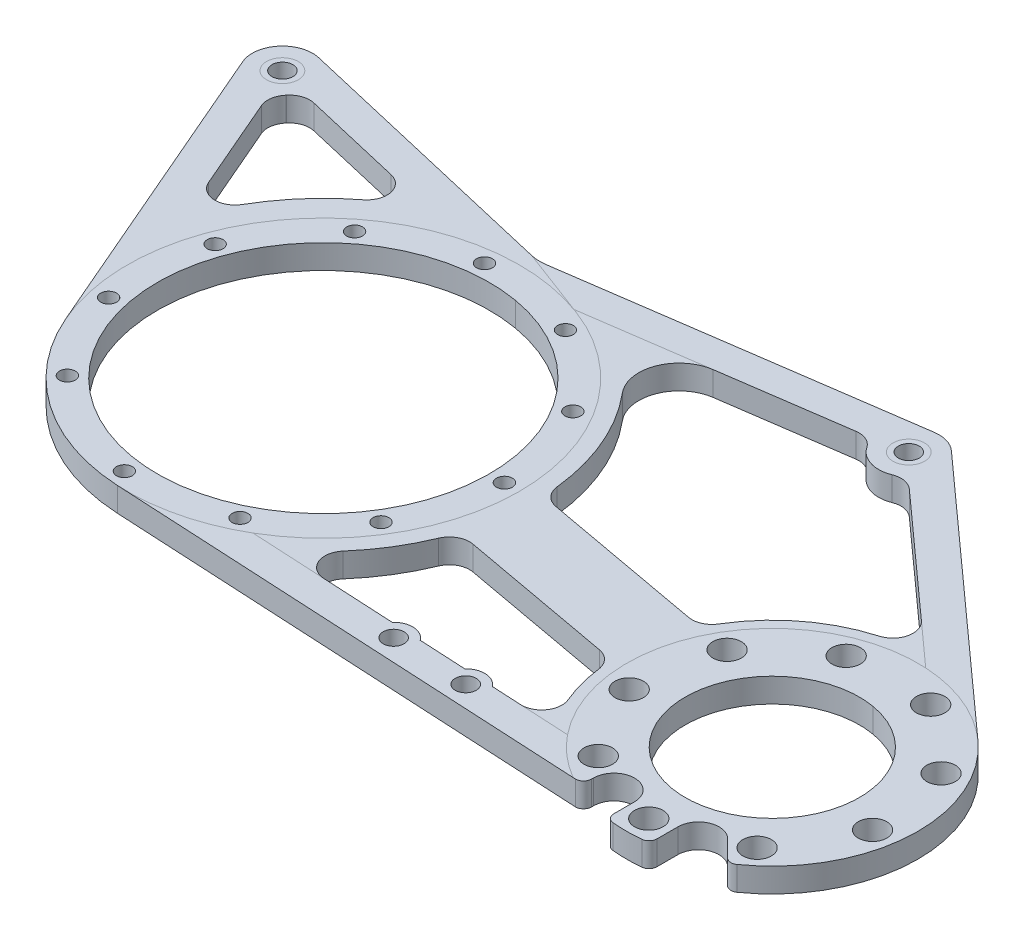
SolidWorks part; units mm, degrees
material "6061-T6 (SS)"
ref_plane "X-Y Datum" through (0, 0, 0) normal (0, 0, 1) x (1, 0, 0)
ref_plane "X-Z Datum" through (0, 0, 0) normal (0, 1, 0) x (1, 0, 0)
ref_plane "Y-Z Datum" through (0, 0, 0) normal (1, 0, 0) x (0, 0, -1)
sketch "Sketch2" plane through (0, 31.3819, 0) normal (0, 1, 0) x (1, 0, 0)
  line L0 (-693.7583, -176.702) -> (-693.7583, -183.2747) construction
  line L1 (-680.0808, -183.2747) -> (-680.0808, -176.702) construction
  line L2 (-668.9846, -172.1058) -> (-663.7197, -177.3707) construction
  line L3 (-693.7583, -176.702) -> (-693.7583, -183.2747)
  line L4 (-680.0808, -183.2747) -> (-680.0808, -176.702)
  line L5 (-668.9846, -172.1058) -> (-663.7197, -177.3707)
  line L6 (-966.641, -0.354) -> (-738.041, -0.354)
  line L7 (-727.7656, -5.5904) -> (-649.7224, -113.0358)
  line L9 (-977.8288, -19.0644) -> (-913.2312, -139.3061)
  line L10 (-706.7583, -177.279) -> (-706.7583, -176.702) construction
  line L11 (-706.7583, -177.279) -> (-706.7583, -176.702)
  line L12 (-861.9259, -171.8334) -> (-709.2983, -179.819)
  line L13 (-858.691, -110.0055) -> (-686.9195, -140.054) construction
  line L14 (-972.26, -24.9963) -> (-955.4664, -39.59) construction
  line L15 (-941.4162, -26.937) -> (-954.1775, -8.712) construction
  line L16 (-751.1929, -14.159) -> (-755.4346, -35.9995) construction
  line L17 (-737.4517, -41.8408) -> (-728.049, -21.6768) construction
  line L18 (-972.26, -24.9963) -> (-955.4664, -39.59)
  line L19 (-941.4162, -26.937) -> (-954.1775, -8.712)
  line L20 (-751.1929, -14.159) -> (-755.4346, -35.9995)
  line L21 (-737.4517, -41.8408) -> (-728.049, -21.6768)
  line L22 (-949.2186, -22.8753) -> (-746.0843, -28.2904)
  line L23 (-739.7146, -30.7335) -> (-656.1751, -105.8723)
  line L24 (-957.9647, -36.1729) -> (-915.5404, -134.527)
  arc A0 (-710.607, -179.4559) -> (-706.7583, -177.279) centre (-709.2983, -177.279) ccw construction
  arc A1 (-693.7583, -176.702) -> (-706.7583, -176.702) centre (-700.2583, -176.702) ccw construction
  arc A2 (-693.7583, -183.2747) -> (-691.4697, -185.8023) centre (-691.2183, -183.2747) ccw construction
  arc A3 (-691.4697, -185.8023) -> (-682.3694, -185.8023) centre (-686.9195, -140.054) ccw construction
  arc A4 (-682.3694, -185.8023) -> (-680.0808, -183.2747) centre (-682.6208, -183.2747) ccw construction
  arc A5 (-668.9846, -172.1058) -> (-680.0808, -176.702) centre (-673.5808, -176.702) ccw construction
  arc A6 (-663.7197, -177.3707) -> (-660.4619, -177.6519) centre (-661.9236, -175.5746) ccw construction
  arc A7 (-660.4619, -177.6519) -> (-710.607, -179.4559) centre (-686.9195, -140.054) ccw construction
  circle A8 centre (-858.691, -110.0055) radius 52.3875 construction
  circle A9 centre (-858.691, -110.0055) radius 61.9125 construction
  circle A10 centre (-738.041, -13.054) radius 12.7 construction
  circle A11 centre (-966.641, -13.054) radius 12.7 construction
  arc A12 (-710.607, -179.4559) -> (-706.7583, -177.279) centre (-709.2983, -177.279) ccw
  arc A13 (-693.7583, -176.702) -> (-706.7583, -176.702) centre (-700.2583, -176.702) ccw
  arc A14 (-693.7583, -183.2747) -> (-691.4697, -185.8023) centre (-691.2183, -183.2747) ccw
  arc A15 (-691.4697, -185.8023) -> (-682.3694, -185.8023) centre (-686.9195, -140.054) ccw
  arc A16 (-682.3694, -185.8023) -> (-680.0808, -183.2747) centre (-682.6208, -183.2747) ccw
  arc A17 (-668.9846, -172.1058) -> (-680.0808, -176.702) centre (-673.5808, -176.702) ccw
  arc A18 (-663.7197, -177.3707) -> (-660.4619, -177.6519) centre (-661.9236, -175.5746) ccw
  arc A19 (-660.4619, -177.6519) -> (-710.607, -179.4559) centre (-686.9195, -140.054) ccw
  circle A20 centre (-858.691, -110.0055) radius 52.3875
  circle A21 centre (-858.691, -110.0055) radius 61.9125
  circle A22 centre (-738.041, -13.054) radius 12.7
  circle A23 centre (-966.641, -13.054) radius 12.7
  circle A31 centre (-864.6648, -166.8424) radius 2.5 construction
  circle A39 centre (-864.6648, -166.8424) radius 2.5
  circle A40 centre (-686.9195, -140.054) radius 27.4955 construction
  circle A41 centre (-686.9195, -140.054) radius 27.4955
  circle A42 centre (-711.9883, -169.9297) radius 4.5 construction
  circle A43 centre (-725.3271, -146.8263) radius 4.5 construction
  circle A44 centre (-720.6945, -120.554) radius 4.5 construction
  circle A45 centre (-700.2583, -103.406) radius 4.5 construction
  circle A46 centre (-673.5808, -103.406) radius 4.5 construction
  circle A47 centre (-653.1446, -120.554) radius 4.5 construction
  circle A48 centre (-648.512, -146.8263) radius 4.5 construction
  circle A49 centre (-661.8508, -169.9297) radius 4.5 construction
  circle A50 centre (-686.9195, -179.054) radius 4.5 construction
  circle A51 centre (-711.9883, -169.9297) radius 4.5
  circle A52 centre (-725.3271, -146.8263) radius 4.5
  circle A53 centre (-720.6945, -120.554) radius 4.5
  circle A54 centre (-700.2583, -103.406) radius 4.5
  circle A55 centre (-673.5808, -103.406) radius 4.5
  circle A56 centre (-653.1446, -120.554) radius 4.5
  circle A57 centre (-648.512, -146.8263) radius 4.5
  circle A58 centre (-661.8508, -169.9297) radius 4.5
  circle A59 centre (-686.9195, -179.054) radius 4.5
  circle A60 centre (-966.641, -13.054) radius 3.3
  circle A61 centre (-738.041, -13.054) radius 3.3
  arc A62 (-955.4664, -39.59) -> (-941.4162, -26.937) centre (-949.2186, -32.4003) ccw construction
  arc A63 (-749.3237, -37.1863) -> (-742.8448, -38.4445) centre (-746.0843, -37.8154) ccw construction
  arc A64 (-742.8448, -38.4445) -> (-749.3237, -37.1863) centre (-746.0843, -37.8154) ccw construction
  arc A65 (-755.4346, -35.9995) -> (-737.4517, -41.8408) centre (-746.0843, -37.8154) ccw construction
  arc A66 (-955.4664, -39.59) -> (-941.4162, -26.937) centre (-949.2186, -32.4003) ccw
  arc A67 (-749.3237, -37.1863) -> (-742.8448, -38.4445) centre (-746.0843, -37.8154) ccw
  arc A68 (-742.8448, -38.4445) -> (-749.3237, -37.1863) centre (-746.0843, -37.8154) ccw
  arc A69 (-755.4346, -35.9995) -> (-737.4517, -41.8408) centre (-746.0843, -37.8154) ccw
  circle A70 centre (-949.2186, -32.4003) radius 3.3
  circle A71 centre (-949.2186, -32.4003) radius 9.525
  circle A72 centre (-746.0843, -37.8154) radius 9.525
  point P94 (-949.2186, -32.4003)
  dimension "D1" = 6.6
  dimension "D2" = 6.6
  dimension "D3" = 6.6
extrude "Boss-Extrude1" add sketch "Sketch2" along normal blind 7.62 contours A21 A39 A20 | A18 A19 A12 L11 A13 L3 A14 A15 A16 L4 A17 L5 A59 A58 A57 A56 A55 A54 A53 A52 A51 A41 | L13 A21 L12 A12 A19 | A21 L13 A19 L23 L21 A69 L20 L22 L19 A66 L18 L24 | A69 A72 A68 A67 | A72 L22 L20 | A72 L21 L23 | A71 L24 L18 | A71 L19 L22 | A71 A66 L22 A70 region at (-700.2583, 31.3819, 168.9016) region at (-773.051, 31.3819, 154.3682) region at (-890.9045, 31.3819, 160.8157) region at (-806.8861, 31.3819, 67.2042) region at (-956.9478, 31.3819, 38.0512) region at (-736.2382, 31.3819, 35.8095) region at (-956.6903, 31.3819, 37.8629) region at (-748.9437, 31.3819, 46.6182) region at (-752.4763, 31.3819, 29.8585) region at (-944.5842, 31.3819, 23.8004)
sketch "Sketch3" plane through (0, 31.3819, 0) normal (0, -1, 0) x (1, 0, 0)
  line L1 (-949.2186, 22.8753) -> (-746.0843, 28.2904) construction
  line L5 (-861.9259, 171.8334) -> (-709.2983, 179.819) construction
  line L6 (-977.8288, 19.0644) -> (-913.2312, 139.3061) construction
  line L7 (-727.7656, 5.5904) -> (-649.7224, 113.0358) construction
  line L13 (-751.1929, 14.159) -> (-755.4346, 35.9995) construction
  line L16 (-966.641, 0.354) -> (-738.041, 0.354) construction
  line L19 (-663.7197, 177.3707) -> (-668.9846, 172.1058)
  line L20 (-680.0808, 176.702) -> (-680.0808, 183.2747)
  line L21 (-693.7583, 183.2747) -> (-693.7583, 176.702)
  line L22 (-706.7583, 176.702) -> (-706.7583, 177.279)
  line L23 (-663.7197, 177.3707) -> (-668.9846, 172.1058)
  line L24 (-680.0808, 176.702) -> (-680.0808, 183.2747)
  line L25 (-693.7583, 183.2747) -> (-693.7583, 176.702)
  line L26 (-706.7583, 176.702) -> (-706.7583, 177.279)
  line L28 (-861.9259, 171.8334) -> (-709.2983, 179.819)
  line L29 (-977.8288, 19.0644) -> (-913.2312, 139.3061)
  line L30 (-727.7656, 5.5904) -> (-649.7224, 113.0358)
  line L31 (-966.641, 0.354) -> (-738.041, 0.354)
  line L34 (-737.4517, 41.8408) -> (-728.049, 21.6768) construction
  line L35 (-972.26, 24.9963) -> (-955.4664, 39.59) construction
  line L36 (-947.0539, 23.1246) -> (-856.9722, 44.1471)
  line L37 (-856.9722, 44.1471) -> (-747.4408, 28.3875)
  line L44 (-941.4162, 26.937) -> (-954.1775, 8.712) construction
  line L45 (-957.9647, 36.1729) -> (-915.5404, 134.527) construction
  line L46 (-739.7146, 30.7335) -> (-656.1751, 105.8723) construction
  line L47 (-861.9259, 171.8334) -> (-709.2983, 179.819)
  line L48 (-977.8288, 19.0644) -> (-913.2312, 139.3061)
  line L49 (-727.7656, 5.5904) -> (-649.7224, 113.0358)
  line L50 (-966.641, 0.354) -> (-738.041, 0.354)
  line L51 (-949.2186, 22.8753) -> (-746.0843, 28.2904)
  line L52 (-751.1929, 14.159) -> (-755.4346, 35.9995)
  line L53 (-737.4517, 41.8408) -> (-728.049, 21.6768)
  line L54 (-972.26, 24.9963) -> (-955.4664, 39.59)
  line L55 (-941.4162, 26.937) -> (-954.1775, 8.712)
  line L56 (-957.9647, 36.1729) -> (-915.5404, 134.527)
  line L57 (-739.7146, 30.7335) -> (-656.1751, 105.8723)
  arc A1 (-737.4517, 41.8408) -> (-755.4346, 35.9995) centre (-746.0843, 37.8154) ccw construction
  circle A3 centre (-966.641, 13.054) radius 12.7
  circle A5 centre (-966.641, 13.054) radius 12.7
  circle A7 centre (-738.041, 13.054) radius 12.7
  circle A9 centre (-738.041, 13.054) radius 12.7
  circle A11 centre (-858.691, 110.0055) radius 61.9125
  circle A13 centre (-858.691, 110.0055) radius 61.9125
  circle A15 centre (-858.691, 110.0055) radius 52.3875
  circle A17 centre (-858.691, 110.0055) radius 52.3875
  circle A19 centre (-686.9195, 140.054) radius 27.4955
  circle A21 centre (-686.9195, 140.054) radius 27.4955
  circle A23 centre (-864.6648, 166.8424) radius 2.5
  circle A25 centre (-864.6648, 166.8424) radius 2.5
  circle A51 centre (-720.6945, 120.554) radius 4.5
  circle A52 centre (-720.6945, 120.554) radius 4.5
  circle A68 centre (-725.3271, 146.8263) radius 4.5
  circle A69 centre (-725.3271, 146.8263) radius 4.5
  circle A70 centre (-711.9883, 169.9297) radius 4.5
  circle A71 centre (-711.9883, 169.9297) radius 4.5
  circle A72 centre (-738.041, 13.054) radius 3.3
  circle A73 centre (-738.041, 13.054) radius 3.3
  circle A74 centre (-966.641, 13.054) radius 3.3
  circle A75 centre (-966.641, 13.054) radius 3.3
  circle A76 centre (-686.9195, 179.054) radius 4.5
  circle A77 centre (-686.9195, 179.054) radius 4.5
  circle A78 centre (-661.8508, 169.9297) radius 4.5
  circle A79 centre (-661.8508, 169.9297) radius 4.5
  circle A80 centre (-648.512, 146.8263) radius 4.5
  circle A81 centre (-648.512, 146.8263) radius 4.5
  circle A82 centre (-653.1446, 120.554) radius 4.5
  circle A83 centre (-653.1446, 120.554) radius 4.5
  circle A84 centre (-673.5808, 103.406) radius 4.5
  circle A85 centre (-673.5808, 103.406) radius 4.5
  circle A86 centre (-700.2583, 103.406) radius 4.5
  circle A87 centre (-700.2583, 103.406) radius 4.5
  arc A95 (-710.607, 179.4559) -> (-660.4619, 177.6519) centre (-686.9195, 140.054) ccw
  arc A96 (-660.4619, 177.6519) -> (-663.7197, 177.3707) centre (-661.9236, 175.5746) ccw
  arc A97 (-680.0808, 176.702) -> (-668.9846, 172.1058) centre (-673.5808, 176.702) ccw
  arc A98 (-680.0808, 183.2747) -> (-682.3694, 185.8023) centre (-682.6208, 183.2747) ccw
  arc A99 (-682.3694, 185.8023) -> (-691.4697, 185.8023) centre (-686.9195, 140.054) ccw
  arc A100 (-691.4697, 185.8023) -> (-693.7583, 183.2747) centre (-691.2183, 183.2747) ccw
  arc A101 (-706.7583, 176.702) -> (-693.7583, 176.702) centre (-700.2583, 176.702) ccw
  arc A102 (-706.7583, 177.279) -> (-710.607, 179.4559) centre (-709.2983, 177.279) ccw
  arc A103 (-710.607, 179.4559) -> (-660.4619, 177.6519) centre (-686.9195, 140.054) ccw
  arc A104 (-660.4619, 177.6519) -> (-663.7197, 177.3707) centre (-661.9236, 175.5746) ccw
  arc A105 (-680.0808, 176.702) -> (-668.9846, 172.1058) centre (-673.5808, 176.702) ccw
  arc A106 (-680.0808, 183.2747) -> (-682.3694, 185.8023) centre (-682.6208, 183.2747) ccw
  arc A107 (-682.3694, 185.8023) -> (-691.4697, 185.8023) centre (-686.9195, 140.054) ccw
  arc A108 (-691.4697, 185.8023) -> (-693.7583, 183.2747) centre (-691.2183, 183.2747) ccw
  arc A109 (-706.7583, 176.702) -> (-693.7583, 176.702) centre (-700.2583, 176.702) ccw
  arc A110 (-706.7583, 177.279) -> (-710.607, 179.4559) centre (-709.2983, 177.279) ccw
  circle A152 centre (-746.0843, 37.8154) radius 9.525
  circle A153 centre (-746.0843, 37.8154) radius 9.525
  circle A154 centre (-949.2186, 32.4003) radius 9.525
  circle A155 centre (-949.2186, 32.4003) radius 9.525
  circle A156 centre (-949.2186, 32.4003) radius 3.3
  circle A157 centre (-949.2186, 32.4003) radius 3.3
  arc A158 (-941.4162, 26.937) -> (-955.4664, 39.59) centre (-949.2186, 32.4003) ccw construction
  arc A159 (-742.8448, 38.4445) -> (-749.3237, 37.1863) centre (-746.0843, 37.8154) ccw
  arc A160 (-749.3237, 37.1863) -> (-742.8448, 38.4445) centre (-746.0843, 37.8154) ccw
  arc A161 (-742.8448, 38.4445) -> (-749.3237, 37.1863) centre (-746.0843, 37.8154) ccw
  arc A162 (-749.3237, 37.1863) -> (-742.8448, 38.4445) centre (-746.0843, 37.8154) ccw
  arc A163 (-737.4517, 41.8408) -> (-755.4346, 35.9995) centre (-746.0843, 37.8154) ccw
  arc A164 (-941.4162, 26.937) -> (-955.4664, 39.59) centre (-949.2186, 32.4003) ccw
  dimension "D24" = 0
  dimension "D25" = 0
  dimension "D26" = 90.0818
  dimension "D27" = 21.0225
  dimension "D1" = 0
  dimension "D2" = 0
  dimension "D3" = 0
  dimension "D4" = 0
  dimension "D5" = 0
  dimension "D6" = 0
  dimension "D14" = 0
  dimension "D15" = 0
  dimension "D16" = 0
  dimension "D17" = 0
  dimension "D18" = 0
  dimension "D19" = 0
  dimension "D20" = 0
  dimension "D21" = 0
  dimension "D22" = 0
  dimension "D23" = 0
  dimension "D52" = 0
  dimension "D53" = 0
  dimension "D54" = 0
  dimension "D55" = 0
ref_point "Point1"
ref_point "Point2"
ref_plane "Plane1" through (-858.691, 31.3819, 110.0055) normal (0.985, 0, 0.1723) x (0.1723, 0, -0.985)
ref_plane "Plane2" through (-686.9195, 31.3819, 140.054) normal (-0.985, 0, -0.1723) x (-0.1723, 0, 0.985)
split line "Split Line1"
split line "Split Line2"
ref_axis "Axis1" through (-858.691, 39.0019, 110.0055) along (0, -1, 0)
ref_axis "Axis2" through (-686.9195, 39.0019, 140.054) along (0, -1, 0)
extrude "Cut-Extrude1" cut sketch "Sketch3" against normal through all contours L36 L55 L51 L52 L37 | A155 L51 L55 L36 | A153 L37 L52 L51 region at (-751.5495, 31.3819, 28.5688) region at (-850.6911, 31.3819, 31.7926) region at (-945.2616, 31.3819, 23.2848)
fillet "Fillet2" radius 12.7 1 edges at (-856.9722, 35.1919, 44.1471)
sketch "Sketch4" plane through (0, 31.3819, 0) normal (0, -1, 0) x (1, 0, 0)
  line L0 (-861.9259, 171.8334) -> (-709.2983, 179.819) construction
  line L1 (-727.7656, 5.5904) -> (-649.7224, 113.0358) construction
  line L2 (-977.8288, 19.0644) -> (-913.2312, 139.3061) construction
  line L4 (-706.7583, 176.702) -> (-706.7583, 177.279)
  line L5 (-663.7197, 177.3707) -> (-668.9846, 172.1058)
  line L6 (-680.0808, 176.702) -> (-680.0808, 183.2747)
  line L7 (-693.7583, 183.2747) -> (-693.7583, 176.702)
  line L8 (-706.7583, 176.702) -> (-706.7583, 177.279)
  line L9 (-663.7197, 177.3707) -> (-668.9846, 172.1058)
  line L10 (-680.0808, 176.702) -> (-680.0808, 183.2747)
  line L11 (-693.7583, 183.2747) -> (-693.7583, 176.702)
  line L13 (-966.641, 0.354) -> (-738.041, 0.354) construction
  line L14 (-861.9259, 171.8334) -> (-709.2983, 179.819)
  line L15 (-727.7656, 5.5904) -> (-649.7224, 113.0358)
  line L16 (-977.8288, 19.0644) -> (-913.2312, 139.3061)
  line L17 (-861.9259, 171.8334) -> (-709.2983, 179.819) construction
  line L19 (-966.641, 0.354) -> (-738.041, 0.354)
  line L20 (-924.6037, 87.863) -> (-948.1369, 33.3048)
  line L21 (-948.1369, 33.3048) -> (-888.5504, 47.2106)
  line L22 (-732.3805, 168.4374) -> (-812.7818, 164.2308) construction
  line L23 (-812.7818, 164.2308) -> (-733.9678, 114.3873) construction
  line L24 (-799.833, 147.0258) -> (-703.8013, 86.2934) construction
  line L25 (-703.8013, 86.2934) -> (-794.9695, 82.1785) construction
  line L26 (-824.108, 49.6832) -> (-755.4008, 39.7974) construction
  line L27 (-798.9847, 74.3695) -> (-701.5009, 78.7695) construction
  line L28 (-701.5009, 78.7695) -> (-739.4428, 44.643) construction
  line L29 (-977.8288, 19.0644) -> (-913.2312, 139.3061) construction
  line L30 (-727.7656, 5.5904) -> (-649.7224, 113.0358) construction
  line L31 (-966.641, 0.354) -> (-738.041, 0.354) construction
  line L32 (-663.7197, 177.3707) -> (-668.9846, 172.1058)
  line L33 (-680.0808, 176.702) -> (-680.0808, 183.2747)
  line L34 (-693.7583, 183.2747) -> (-693.7583, 176.702)
  line L35 (-706.7583, 176.702) -> (-706.7583, 177.279)
  line L36 (-663.7197, 177.3707) -> (-668.9846, 172.1058)
  line L37 (-680.0808, 176.702) -> (-680.0808, 183.2747)
  line L38 (-693.7583, 183.2747) -> (-693.7583, 176.702)
  line L39 (-706.7583, 176.702) -> (-706.7583, 177.279)
  line L40 (-949.2186, 22.8753) -> (-746.0843, 28.2904) construction
  line L41 (-751.1929, 14.159) -> (-755.4346, 35.9995) construction
  line L42 (-737.4517, 41.8408) -> (-728.049, 21.6768) construction
  line L43 (-972.26, 24.9963) -> (-955.4664, 39.59) construction
  line L44 (-941.4162, 26.937) -> (-954.1775, 8.712) construction
  line L45 (-957.9647, 36.1729) -> (-915.5404, 134.527) construction
  line L46 (-739.7146, 30.7335) -> (-656.1751, 105.8723) construction
  line L47 (-861.9259, 171.8334) -> (-709.2983, 179.819)
  line L48 (-977.8288, 19.0644) -> (-913.2312, 139.3061)
  line L49 (-727.7656, 5.5904) -> (-649.7224, 113.0358)
  line L50 (-966.641, 0.354) -> (-738.041, 0.354)
  line L51 (-949.2186, 22.8753) -> (-746.0843, 28.2904)
  line L52 (-751.1929, 14.159) -> (-755.4346, 35.9995)
  line L53 (-737.4517, 41.8408) -> (-728.049, 21.6768)
  line L54 (-972.26, 24.9963) -> (-955.4664, 39.59)
  line L55 (-941.4162, 26.937) -> (-954.1775, 8.712)
  line L56 (-957.9647, 36.1729) -> (-915.5404, 134.527)
  line L57 (-739.7146, 30.7335) -> (-656.1751, 105.8723)
  line L58 (-947.0539, 23.1246) -> (-859.3005, 43.6037) construction
  line L60 (-854.6056, 43.8066) -> (-747.4408, 28.3875) construction
  circle A1 centre (-858.691, 110.0055) radius 52.3875
  circle A2 centre (-858.691, 110.0055) radius 52.3875
  circle A3 centre (-858.691, 110.0055) radius 61.9125
  circle A4 centre (-858.691, 110.0055) radius 61.9125
  circle A5 centre (-738.041, 13.054) radius 12.7
  circle A6 centre (-738.041, 13.054) radius 12.7
  circle A7 centre (-966.641, 13.054) radius 12.7
  circle A8 centre (-966.641, 13.054) radius 12.7
  circle A17 centre (-864.6648, 166.8424) radius 2.5
  circle A18 centre (-864.6648, 166.8424) radius 2.5
  circle A19 centre (-686.9195, 140.054) radius 27.4955
  circle A20 centre (-686.9195, 140.054) radius 27.4955
  circle A21 centre (-725.3271, 146.8263) radius 4.5
  circle A22 centre (-725.3271, 146.8263) radius 4.5
  circle A23 centre (-720.6945, 120.554) radius 4.5
  circle A24 centre (-720.6945, 120.554) radius 4.5
  circle A31 centre (-661.8508, 169.9297) radius 4.5
  circle A32 centre (-661.8508, 169.9297) radius 4.5
  circle A33 centre (-686.9195, 179.054) radius 4.5
  circle A34 centre (-686.9195, 179.054) radius 4.5
  circle A35 centre (-966.641, 13.054) radius 3.3
  circle A36 centre (-966.641, 13.054) radius 3.3
  circle A37 centre (-738.041, 13.054) radius 3.3
  circle A38 centre (-738.041, 13.054) radius 3.3
  circle A39 centre (-711.9883, 169.9297) radius 4.5
  circle A40 centre (-711.9883, 169.9297) radius 4.5
  circle A41 centre (-700.2583, 103.406) radius 4.5
  circle A42 centre (-700.2583, 103.406) radius 4.5
  circle A43 centre (-673.5808, 103.406) radius 4.5
  circle A44 centre (-673.5808, 103.406) radius 4.5
  circle A45 centre (-653.1446, 120.554) radius 4.5
  circle A46 centre (-653.1446, 120.554) radius 4.5
  circle A47 centre (-648.512, 146.8263) radius 4.5
  circle A48 centre (-648.512, 146.8263) radius 4.5
  arc A49 (-888.5504, 47.2106) -> (-924.6037, 87.863) centre (-858.691, 110.0055) cw
  arc A50 (-732.3805, 168.4374) -> (-733.9678, 114.3873) centre (-686.9195, 140.054) ccw construction
  arc A51 (-799.833, 147.0258) -> (-794.9695, 82.1785) centre (-858.691, 110.0055) cw construction
  arc A52 (-824.108, 49.6832) -> (-798.9847, 74.3695) centre (-858.691, 110.0055) ccw construction
  arc A53 (-737.4517, 41.8408) -> (-755.4346, 35.9995) centre (-746.0843, 37.8154) ccw construction
  circle A54 centre (-966.641, 13.054) radius 12.7
  circle A55 centre (-966.641, 13.054) radius 12.7
  arc A56 (-706.7583, 177.279) -> (-710.607, 179.4559) centre (-709.2983, 177.279) ccw
  arc A57 (-710.607, 179.4559) -> (-660.4619, 177.6519) centre (-686.9195, 140.054) ccw
  arc A58 (-660.4619, 177.6519) -> (-663.7197, 177.3707) centre (-661.9236, 175.5746) ccw
  arc A59 (-680.0808, 176.702) -> (-668.9846, 172.1058) centre (-673.5808, 176.702) ccw
  arc A60 (-680.0808, 183.2747) -> (-682.3694, 185.8023) centre (-682.6208, 183.2747) ccw
  arc A61 (-682.3694, 185.8023) -> (-691.4697, 185.8023) centre (-686.9195, 140.054) ccw
  arc A62 (-691.4697, 185.8023) -> (-693.7583, 183.2747) centre (-691.2183, 183.2747) ccw
  arc A63 (-706.7583, 176.702) -> (-693.7583, 176.702) centre (-700.2583, 176.702) ccw
  arc A64 (-706.7583, 177.279) -> (-710.607, 179.4559) centre (-709.2983, 177.279) ccw
  arc A65 (-710.607, 179.4559) -> (-660.4619, 177.6519) centre (-686.9195, 140.054) ccw
  arc A66 (-660.4619, 177.6519) -> (-663.7197, 177.3707) centre (-661.9236, 175.5746) ccw
  arc A67 (-680.0808, 176.702) -> (-668.9846, 172.1058) centre (-673.5808, 176.702) ccw
  arc A68 (-680.0808, 183.2747) -> (-682.3694, 185.8023) centre (-682.6208, 183.2747) ccw
  arc A69 (-682.3694, 185.8023) -> (-691.4697, 185.8023) centre (-686.9195, 140.054) ccw
  arc A70 (-691.4697, 185.8023) -> (-693.7583, 183.2747) centre (-691.2183, 183.2747) ccw
  arc A71 (-706.7583, 176.702) -> (-693.7583, 176.702) centre (-700.2583, 176.702) ccw
  circle A72 centre (-738.041, 13.054) radius 12.7
  circle A73 centre (-738.041, 13.054) radius 12.7
  circle A74 centre (-858.691, 110.0055) radius 61.9125
  circle A75 centre (-858.691, 110.0055) radius 61.9125
  circle A76 centre (-858.691, 110.0055) radius 52.3875
  circle A77 centre (-858.691, 110.0055) radius 52.3875
  circle A78 centre (-686.9195, 140.054) radius 27.4955
  circle A79 centre (-686.9195, 140.054) radius 27.4955
  circle A80 centre (-864.6648, 166.8424) radius 2.5
  circle A81 centre (-864.6648, 166.8424) radius 2.5
  circle A96 centre (-720.6945, 120.554) radius 4.5
  circle A97 centre (-720.6945, 120.554) radius 4.5
  circle A98 centre (-725.3271, 146.8263) radius 4.5
  circle A99 centre (-725.3271, 146.8263) radius 4.5
  circle A100 centre (-711.9883, 169.9297) radius 4.5
  circle A101 centre (-711.9883, 169.9297) radius 4.5
  circle A102 centre (-738.041, 13.054) radius 3.3
  circle A103 centre (-738.041, 13.054) radius 3.3
  circle A104 centre (-966.641, 13.054) radius 3.3
  circle A105 centre (-966.641, 13.054) radius 3.3
  circle A106 centre (-686.9195, 179.054) radius 4.5
  circle A107 centre (-686.9195, 179.054) radius 4.5
  circle A108 centre (-661.8508, 169.9297) radius 4.5
  circle A109 centre (-661.8508, 169.9297) radius 4.5
  circle A110 centre (-648.512, 146.8263) radius 4.5
  circle A111 centre (-648.512, 146.8263) radius 4.5
  circle A112 centre (-653.1446, 120.554) radius 4.5
  circle A113 centre (-653.1446, 120.554) radius 4.5
  circle A114 centre (-673.5808, 103.406) radius 4.5
  circle A115 centre (-673.5808, 103.406) radius 4.5
  circle A116 centre (-700.2583, 103.406) radius 4.5
  circle A117 centre (-700.2583, 103.406) radius 4.5
  circle A118 centre (-746.0843, 37.8154) radius 9.525
  circle A119 centre (-746.0843, 37.8154) radius 9.525
  circle A120 centre (-949.2186, 32.4003) radius 9.525
  circle A121 centre (-949.2186, 32.4003) radius 9.525
  circle A122 centre (-949.2186, 32.4003) radius 3.3
  circle A123 centre (-949.2186, 32.4003) radius 3.3
  arc A124 (-941.4162, 26.937) -> (-955.4664, 39.59) centre (-949.2186, 32.4003) ccw construction
  arc A125 (-742.8448, 38.4445) -> (-749.3237, 37.1863) centre (-746.0843, 37.8154) ccw
  arc A126 (-749.3237, 37.1863) -> (-742.8448, 38.4445) centre (-746.0843, 37.8154) ccw
  arc A127 (-742.8448, 38.4445) -> (-749.3237, 37.1863) centre (-746.0843, 37.8154) ccw
  arc A128 (-749.3237, 37.1863) -> (-742.8448, 38.4445) centre (-746.0843, 37.8154) ccw
  arc A129 (-737.4517, 41.8408) -> (-755.4346, 35.9995) centre (-746.0843, 37.8154) ccw
  arc A130 (-941.4162, 26.937) -> (-955.4664, 39.59) centre (-949.2186, 32.4003) ccw
  arc A135 (-710.607, 179.4559) -> (-660.4619, 177.6519) centre (-686.9195, 140.054) ccw
  arc A136 (-660.4619, 177.6519) -> (-663.7197, 177.3707) centre (-661.9236, 175.5746) ccw
  arc A137 (-680.0808, 176.702) -> (-668.9846, 172.1058) centre (-673.5808, 176.702) ccw
  arc A138 (-680.0808, 183.2747) -> (-682.3694, 185.8023) centre (-682.6208, 183.2747) ccw
  arc A139 (-682.3694, 185.8023) -> (-691.4697, 185.8023) centre (-686.9195, 140.054) ccw
  arc A140 (-691.4697, 185.8023) -> (-693.7583, 183.2747) centre (-691.2183, 183.2747) ccw
  arc A141 (-706.7583, 176.702) -> (-693.7583, 176.702) centre (-700.2583, 176.702) ccw
  arc A142 (-706.7583, 177.279) -> (-710.607, 179.4559) centre (-709.2983, 177.279) ccw
  arc A143 (-710.607, 179.4559) -> (-660.4619, 177.6519) centre (-686.9195, 140.054) ccw
  arc A144 (-660.4619, 177.6519) -> (-663.7197, 177.3707) centre (-661.9236, 175.5746) ccw
  arc A145 (-680.0808, 176.702) -> (-668.9846, 172.1058) centre (-673.5808, 176.702) ccw
  arc A146 (-680.0808, 183.2747) -> (-682.3694, 185.8023) centre (-682.6208, 183.2747) ccw
  arc A147 (-682.3694, 185.8023) -> (-691.4697, 185.8023) centre (-686.9195, 140.054) ccw
  arc A148 (-691.4697, 185.8023) -> (-693.7583, 183.2747) centre (-691.2183, 183.2747) ccw
  arc A149 (-706.7583, 176.702) -> (-693.7583, 176.702) centre (-700.2583, 176.702) ccw
  arc A150 (-706.7583, 177.279) -> (-710.607, 179.4559) centre (-709.2983, 177.279) ccw
  dimension "D26" = 7.62
  dimension "D29" = 7.62
  dimension "D30" = 7.62
  dimension "D35" = 0
  dimension "D39" = 7.62
  dimension "D27" = 0
  dimension "D28" = 0
  dimension "D31" = 10.16
  dimension "D32" = 7.62
  dimension "D33" = 93.2524
  dimension "D34" = 49.8435
  dimension "D36" = 91.1683
  dimension "D37" = 4.1149
  dimension "D38" = 10.16
  dimension "D40" = 7.62
  dimension "D67" = 10.16
  dimension "D68" = 10.16
  dimension "D69" = 10.16
  dimension "D1" = 0
  dimension "D2" = 0
  dimension "D3" = 0
  dimension "D4" = 0
  dimension "D9" = 0
  dimension "D10" = 0
  dimension "D11" = 0
  dimension "D12" = 0
  dimension "D16" = 0
  dimension "D17" = 0
  dimension "D18" = 0
  dimension "D19" = 0
  dimension "D20" = 0
  dimension "D21" = 0
  dimension "D22" = 0
  dimension "D23" = 0
  dimension "D24" = 0
  dimension "D25" = 0
  dimension "D41" = 0
  dimension "D42" = 0
  dimension "D43" = 0
  dimension "D51" = 0
  dimension "D52" = 0
  dimension "D53" = 0
  dimension "D54" = 0
  dimension "D55" = 0
  dimension "D56" = 0
  dimension "D57" = 0
  dimension "D58" = 0
  dimension "D59" = 0
  dimension "D60" = 0
  dimension "D61" = 0
  dimension "D62" = 0
  dimension "D63" = 0
  dimension "D64" = 0
  dimension "D65" = 0
  dimension "D66" = 0
extrude "Cut-Extrude2" cut sketch "Sketch4" against normal through all contours L21 A49 L20 A8 | A52 L26 A6 L28 L27 | L24 A51 L25 | A50 L22 L23 region at (-829.4195, 31.3819, 24.9298) region at (-921.8341, 31.3819, 54.9859)
fillet "Fillet3" [suppressed] radius 6.604
split line "Split Line3"
sketch "Sketch2<4>" plane through (0, 31.3819, 0) normal (0, 1, 0) x (1, 0, 0) same geometry as "Sketch2"
pattern_circular "CirPattern2" count 11 every 32 about axis through (-858.691, 39.0019, 110.0055) along (0, -1, 0) reverse direction yes of face at (-867.1648, 39.0019, 166.8424)
sketch "Sketch5" plane through (0, 39.0019, 0) normal (0, 1, 0) x (1, 0, 0)
  circle A0 centre (-949.2186, -32.4003) radius 5
  circle A1 centre (-746.0843, -37.8154) radius 5
  dimension "D1" = 10
split line "Split Line4"
sketch "Sketch6" [suppressed] plane through (0, 31.3819, 0) normal (0, -1, 0) x (1, 0, 0)
  line L0 (-743.6056, 167.8501) -> (-792.0577, 165.3151) construction
  line L1 (-724.7926, 85.346) -> (-785.1492, 82.6217) construction
  line L2 (-724.7926, 85.346) -> (-785.1492, 82.6217)
  line L3 (-791.5915, 128.2378) -> (-796.8267, 141.9391)
  line L4 (-743.6056, 167.8501) -> (-781.2512, 165.8805)
  line L5 (-781.2512, 165.8805) -> (-792.0577, 165.3151)
  arc A0 (-791.8001, 91.022) -> (-791.5915, 128.2378) centre (-858.691, 110.0055) ccw construction
  arc A1 (-791.8001, 91.022) -> (-791.5915, 128.2378) centre (-858.691, 110.0055) ccw
  circle A2 centre (-780.3284, 148.243) radius 17.6616 construction
  circle A3 centre (-744.0706, 102.1866) radius 14.9639 construction
  arc A4 (-737.0797, 158.9293) -> (-739.7578, 131.0856) centre (-686.9195, 140.054) ccw construction
  arc A5 (-724.7926, 85.346) -> (-721.5605, 97.5247) centre (-725.0904, 91.9433) ccw construction
  arc A6 (-737.0797, 158.9293) -> (-743.6056, 167.8501) centre (-743.2606, 161.2551) ccw construction
  arc A7 (-737.0797, 158.9293) -> (-739.7578, 131.0856) centre (-686.9195, 140.054) ccw
  arc A8 (-737.0797, 158.9293) -> (-743.6056, 167.8501) centre (-743.2606, 161.2551) ccw
  arc A9 (-724.7926, 85.346) -> (-721.5605, 97.5247) centre (-725.0904, 91.9433) ccw
  arc A10 (-791.8001, 91.022) -> (-785.1492, 82.6217) centre (-785.447, 89.219) ccw construction
  arc A11 (-791.8001, 91.022) -> (-785.1492, 82.6217) centre (-785.447, 89.219) ccw
  arc A13 (-739.7578, 131.0856) -> (-731.5964, 110.4517) centre (-686.9195, 140.054) ccw
  arc A14 (-721.5605, 97.5247) -> (-731.5964, 110.4517) centre (-640.5401, 170.7843) cw
  arc A15 (-792.0577, 165.3151) -> (-798.1017, 160.3912) centre (-791.7127, 158.7201) ccw
  arc A17 (-792.0577, 165.3151) -> (-795.2425, 153.1386) centre (-791.7127, 158.7201) ccw construction
  arc A18 (-798.1017, 160.3912) -> (-796.8267, 141.9391) centre (-767.2093, 153.2558) ccw
  dimension "D3" = 31.7058
  dimension "D1" = 11.2631
  dimension "D2" = 22.5101
extrude "Cut-Extrude3" [suppressed] cut sketch "Sketch6" against normal through all
sketch "Sketch7" plane through (0, 31.3819, 0) normal (0, -1, 0) x (1, 0, 0)
  line L0 (-859.3005, 43.6037) -> (-836.8375, 52.0781)
  arc A0 (-915.5404, 134.527) -> (-861.9259, 171.8334) centre (-858.691, 110.0055) ccw construction
split line "Split Line5"
sketch "Sketch8" plane through (0, 39.0019, 0) normal (0, 1, 0) x (1, 0, 0)
  line L0 (-859.3005, -43.6037) -> (-836.8375, -52.0781) construction
  line L1 (-859.3005, -43.6037) -> (-836.8375, -52.0781)
  line L2 (-732.3805, -168.4374) -> (-812.7818, -164.2308) construction
  line L3 (-824.108, -49.6832) -> (-755.4008, -39.7974) construction
  line L4 (-701.5009, -78.7695) -> (-739.4428, -44.643) construction
  line L5 (-732.3805, -168.4374) -> (-812.7818, -164.2308)
  line L6 (-824.108, -49.6832) -> (-755.4008, -39.7974)
  line L7 (-709.5634, -179.8051) -> (-709.2983, -179.819)
  line L8 (-668.9846, -172.1058) -> (-663.7197, -177.3707)
  line L9 (-680.0808, -183.2747) -> (-680.0808, -176.702)
  line L10 (-693.7583, -176.702) -> (-693.7583, -183.2747)
  line L11 (-706.7583, -177.279) -> (-706.7583, -176.702)
  line L12 (-709.5634, -179.8051) -> (-709.2983, -179.819)
  line L13 (-668.9846, -172.1058) -> (-663.7197, -177.3707)
  line L14 (-680.0808, -183.2747) -> (-680.0808, -176.702)
  line L15 (-693.7583, -176.702) -> (-693.7583, -183.2747)
  line L16 (-706.7583, -177.279) -> (-706.7583, -176.702)
  line L17 (-701.5009, -78.7695) -> (-739.4428, -44.643)
  line L18 (-701.5009, -78.7695) -> (-684.402, -94.149)
  line L19 (-824.108, -49.6832) -> (-837.9186, -51.6702)
  line L20 (-732.3805, -168.4374) -> (-722.6816, -168.9449)
  line L21 (-812.7818, -164.2308) -> (-827.4586, -163.4628)
  circle A0 centre (-746.0843, -37.8154) radius 9.525 construction
  circle A1 centre (-746.0843, -37.8154) radius 9.525 construction
  arc A2 (-739.4428, -44.643) -> (-755.4008, -39.7974) centre (-746.0843, -37.8154) cw
  arc A3 (-915.5404, -134.527) -> (-861.9259, -171.8334) centre (-858.691, -110.0055) ccw
  arc A4 (-836.8375, -52.0781) -> (-915.5404, -134.527) centre (-858.691, -110.0055) ccw
  arc A5 (-861.9259, -171.8334) -> (-836.8375, -52.0781) centre (-858.691, -110.0055) ccw
  arc A6 (-915.5404, -134.527) -> (-861.9259, -171.8334) centre (-858.691, -110.0055) ccw
  arc A7 (-836.8375, -52.0781) -> (-915.5404, -134.527) centre (-858.691, -110.0055) ccw
  arc A8 (-861.9259, -171.8334) -> (-836.8375, -52.0781) centre (-858.691, -110.0055) ccw
  arc A16 (-710.607, -179.4559) -> (-709.5634, -179.8051) centre (-709.2983, -177.279) ccw
  arc A17 (-656.1751, -105.8723) -> (-710.607, -179.4559) centre (-686.9195, -140.054) ccw
  arc A18 (-660.4619, -177.6519) -> (-656.1751, -105.8723) centre (-686.9195, -140.054) ccw
  arc A19 (-663.7197, -177.3707) -> (-660.4619, -177.6519) centre (-661.9236, -175.5746) ccw
  arc A20 (-668.9846, -172.1058) -> (-680.0808, -176.702) centre (-673.5808, -176.702) ccw
  arc A21 (-682.3694, -185.8023) -> (-680.0808, -183.2747) centre (-682.6208, -183.2747) ccw
  arc A22 (-691.4697, -185.8023) -> (-682.3694, -185.8023) centre (-686.9195, -140.054) ccw
  arc A23 (-693.7583, -183.2747) -> (-691.4697, -185.8023) centre (-691.2183, -183.2747) ccw
  arc A24 (-693.7583, -176.702) -> (-706.7583, -176.702) centre (-700.2583, -176.702) ccw
  arc A25 (-709.2983, -179.819) -> (-706.7583, -177.279) centre (-709.2983, -177.279) ccw
  arc A26 (-710.607, -179.4559) -> (-709.5634, -179.8051) centre (-709.2983, -177.279) ccw
  arc A27 (-656.1751, -105.8723) -> (-710.607, -179.4559) centre (-686.9195, -140.054) ccw
  arc A28 (-660.4619, -177.6519) -> (-656.1751, -105.8723) centre (-686.9195, -140.054) ccw
  arc A29 (-663.7197, -177.3707) -> (-660.4619, -177.6519) centre (-661.9236, -175.5746) ccw
  arc A30 (-668.9846, -172.1058) -> (-680.0808, -176.702) centre (-673.5808, -176.702) ccw
  arc A31 (-682.3694, -185.8023) -> (-680.0808, -183.2747) centre (-682.6208, -183.2747) ccw
  arc A32 (-691.4697, -185.8023) -> (-682.3694, -185.8023) centre (-686.9195, -140.054) ccw
  arc A33 (-693.7583, -183.2747) -> (-691.4697, -185.8023) centre (-691.2183, -183.2747) ccw
  arc A34 (-693.7583, -176.702) -> (-706.7583, -176.702) centre (-700.2583, -176.702) ccw
  arc A35 (-709.2983, -179.819) -> (-706.7583, -177.279) centre (-709.2983, -177.279) ccw
  dimension "D1" = 0
  dimension "D2" = 0
split line "Split Line6"
fillet "Fillet4" radius 6.3754 4 edges at (-940.1078, 35.1919, 35.1786) (-944.8714, 35.1919, 40.8754) (-888.5504, 35.1919, 47.2106) (-924.6037, 35.1919, 87.863)
sketch "Sketch9" plane through (0, 31.3819, 0) normal (0, -1, 0) x (1, 0, 0)
  line L8 (-732.3805, 168.4374) -> (-812.7818, 164.2308)
  line L9 (-722.6816, 168.9449) -> (-732.3805, 168.4374)
  line L10 (-701.5009, 78.7695) -> (-684.402, 94.149)
  line L11 (-739.4428, 44.643) -> (-701.5009, 78.7695)
  line L12 (-824.108, 49.6832) -> (-755.4008, 39.7974)
  line L13 (-837.9186, 51.6702) -> (-824.108, 49.6832)
  line L14 (-836.8375, 52.0781) -> (-837.9186, 51.6702)
  line L15 (-812.7818, 164.2308) -> (-827.4586, 163.4628)
  line L16 (-732.3805, 168.4374) -> (-812.7818, 164.2308)
  line L17 (-722.6816, 168.9449) -> (-732.3805, 168.4374)
  line L18 (-701.5009, 78.7695) -> (-684.402, 94.149)
  line L19 (-739.4428, 44.643) -> (-701.5009, 78.7695)
  line L20 (-824.108, 49.6832) -> (-755.4008, 39.7974)
  line L21 (-837.9186, 51.6702) -> (-824.108, 49.6832)
  line L22 (-836.8375, 52.0781) -> (-837.9186, 51.6702)
  line L23 (-812.7818, 164.2308) -> (-827.4586, 163.4628)
  arc A3 (-722.6816, 168.9449) -> (-684.402, 94.149) centre (-686.9195, 140.054) ccw
  arc A4 (-739.4428, 44.643) -> (-755.4008, 39.7974) centre (-746.0843, 37.8154) ccw
  arc A5 (-836.8375, 52.0781) -> (-827.4586, 163.4628) centre (-858.691, 110.0055) ccw
  arc A6 (-722.6816, 168.9449) -> (-684.402, 94.149) centre (-686.9195, 140.054) ccw
  arc A7 (-739.4428, 44.643) -> (-755.4008, 39.7974) centre (-746.0843, 37.8154) ccw
  arc A8 (-836.8375, 52.0781) -> (-827.4586, 163.4628) centre (-858.691, 110.0055) ccw
  dimension "D1" = 0
split line "Split Line7"
sketch "Sketch10" plane through (0, 31.3819, 0) normal (0, -1, 0) x (1, 0, 0)
  line L0 (-818.9129, 163.91) -> (-726.8377, 168.7274)
  line L1 (-732.3805, 168.4374) -> (-812.7818, 164.2308) construction
  line L2 (-837.9186, 51.6702) -> (-824.108, 49.6832) construction
  line L3 (-812.7818, 164.2308) -> (-827.4586, 163.4628) construction
  line L4 (-798.0516, 122.496) -> (-732.5518, 134.4586) construction
  line L5 (-795.007, 130.7981) -> (-736.0453, 141.5666)
  line L6 (-791.745, 107.5102) -> (-731.1295, 118.5807)
  line L7 (-701.5009, 78.7695) -> (-684.402, 94.149) construction
  line L8 (-828.3256, 50.29) -> (-755.4008, 39.7974)
  line L9 (-739.4428, 44.643) -> (-687.9956, 90.9168)
  arc A0 (-828.3256, 50.29) -> (-791.745, 107.5102) centre (-858.691, 110.0055) ccw
  arc A1 (-731.1295, 118.5807) -> (-687.9956, 90.9168) centre (-686.9195, 140.054) ccw
  arc A2 (-818.9129, 163.91) -> (-795.007, 130.7981) centre (-858.691, 110.0055) cw
  arc A3 (-835.0444, 47.3251) -> (-824.896, 167.8491) centre (-858.691, 110.0055) ccw
  arc A4 (-835.0444, 47.3251) -> (-824.896, 167.8491) centre (-858.691, 110.0055) ccw construction
  arc A5 (-836.8375, 52.0781) -> (-827.4586, 163.4628) centre (-858.691, 110.0055) ccw construction
  arc A6 (-722.6816, 168.9449) -> (-684.402, 94.149) centre (-686.9195, 140.054) ccw construction
  arc A7 (-726.8377, 168.7274) -> (-736.0453, 141.5666) centre (-686.9195, 140.054) ccw
  arc A8 (-725.1514, 170.9401) -> (-684.2281, 90.9787) centre (-686.9195, 140.054) ccw
  arc A9 (-725.1514, 170.9401) -> (-684.2281, 90.9787) centre (-686.9195, 140.054) ccw construction
  arc A10 (-755.4008, 39.7974) -> (-739.4428, 44.643) centre (-746.0843, 37.8154) cw
  arc A11 (-739.4428, 44.643) -> (-755.4008, 39.7974) centre (-746.0843, 37.8154) ccw construction
  dimension "D3" = 41.4139
  dimension "D4" = 34.2689
  dimension "D5" = 7.62
  dimension "D6" = 15.875
  dimension "D1" = 5.08
  dimension "D2" = 3.175
extrude "Cut-Extrude4" cut sketch "Sketch10" against normal through all contours L5 A7 L0 A2 | L9 A1 L6 A0 L8 A10
fillet "Fillet5" radius 6.3754 8 edges at (-687.9956, 35.1919, 90.9168) (-739.4428, 35.1919, 44.643) (-755.4008, 35.1919, 39.7974) (-731.1295, 35.1919, 118.5807) (-795.007, 35.1919, 130.7981) (-736.0453, 35.1919, 141.5666) (-726.8377, 35.1919, 168.7274) (-818.9129, 35.1919, 163.91)
fillet "Fillet6" radius 6.3754 1 edges at (-791.745, 35.1919, 107.5102)
fillet "Fillet7" radius 12.7 1 edges at (-828.3256, 35.1919, 50.29)
sketch3d "3DSketch1"
  arc A3 (-738.3594, 31.3819, 168.1246) -> (-732.1581, 31.3819, 159.2658) centre (-738.0263, 31.3819, 161.7579) ccw construction
  arc A4 (-732.1581, 31.3819, 159.2658) -> (-735.6872, 31.3819, 146.1648) centre (-686.9195, 31.3819, 140.054) ccw
  arc A5 (-738.3594, 31.3819, 168.1246) -> (-732.1581, 31.3819, 159.2658) centre (-738.0263, 31.3819, 161.7579) ccw
  circle A6 centre (-752.529, 24.9199, 171.23) radius 5 construction
  circle A7 centre (-776.621, 24.7819, 169.8829) radius 5 construction
  point P6 (-686.9195, -17.7671, 140.054)
  point P14 (-738.0263, 37.7573, 161.7579)
  point P16 (-752.529, 29.9199, 171.23)
  point P18 (-776.621, 29.7819, 169.8829)
  point P23 (-738.0263, 37.7573, 161.7579)
  dimension "D2" = 10
  dimension "D3" = 10
  dimension "D4" = 39.9891
  dimension "D7" = 30.8815
  dimension "D1" = 24.13
  dimension "D5" = 18.4881
  dimension "D8" = 22.1218
  dimension "D9" = 10.8136
  dimension "D10" = 13.568
sketch "Sketch11" plane through (0, 31.3819, 0) normal (0, -1, 0) x (1, 0, 0)
  line L0 (-738.3594, 168.1246) -> (-803.8217, 164.6996) construction
  line L1 (-781.0982, 165.8885) -> (-771.7515, 166.3775)
  line L2 (-756.931, 167.1529) -> (-747.7256, 167.6346)
  circle A0 centre (-752.529, 171.23) radius 5 construction
  circle A1 centre (-776.621, 169.8829) radius 5 construction
  circle A2 centre (-752.529, 171.23) radius 5 construction
  circle A3 centre (-776.621, 169.8829) radius 5 construction
  circle A4 centre (-776.621, 169.8829) radius 3.3
  circle A5 centre (-752.529, 171.23) radius 3.3
  arc A6 (-781.0982, 165.8885) -> (-771.7515, 166.3775) centre (-776.621, 169.8829) ccw construction
  arc A7 (-781.0982, 165.8885) -> (-771.7515, 166.3775) centre (-776.621, 169.8829) ccw
  arc A8 (-756.931, 167.1529) -> (-747.7256, 167.6346) centre (-752.529, 171.23) ccw
  dimension "D1" = 6.6
  dimension "D2" = 1
  dimension "D3" = 1
extrude "Cut-Extrude5" cut sketch "Sketch11" against normal through all contours A5 | A4
sketch "Sketch12" plane through (0, 31.3819, 0) normal (0, -1, 0) x (1, 0, 0)
  line L0 (-756.931, 167.1529) -> (-747.7256, 167.6346) construction
  line L1 (-781.0982, 165.8885) -> (-771.7515, 166.3775) construction
  line L2 (-756.931, 167.1529) -> (-747.7256, 167.6346)
  line L3 (-781.0982, 165.8885) -> (-771.7515, 166.3775)
  arc A0 (-756.931, 167.1529) -> (-747.7256, 167.6346) centre (-752.529, 171.23) ccw construction
  arc A1 (-781.0982, 165.8885) -> (-771.7515, 166.3775) centre (-776.621, 169.8829) ccw construction
  arc A2 (-756.931, 167.1529) -> (-747.7256, 167.6346) centre (-752.529, 171.23) ccw
  arc A3 (-781.0982, 165.8885) -> (-771.7515, 166.3775) centre (-776.621, 169.8829) ccw
extrude "Boss-Extrude2" add sketch "Sketch12" against normal up to surface (7.62 mm away) up to face at (-751.0843, 39.0019, 37.8154)
